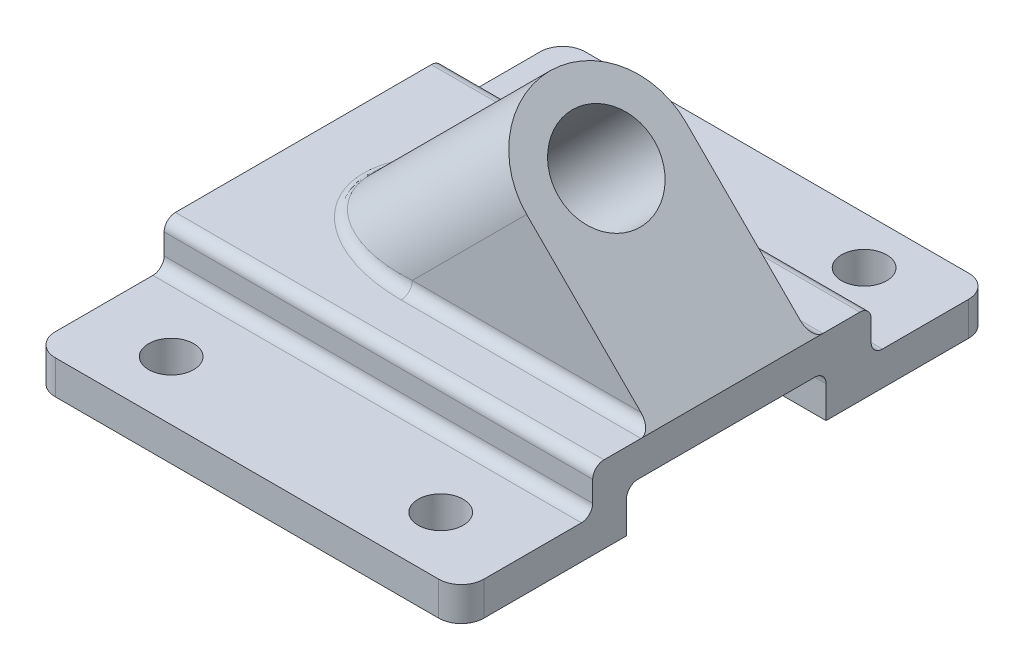
SolidWorks part; units mm, degrees
ref_plane "Front Plane" through (0, 0, 0) normal (0, 0, 1) x (1, 0, 0)
ref_plane "Top Plane" through (0, 0, 0) normal (0, 1, 0) x (1, 0, 0)
ref_plane "Right Plane" through (0, 0, 0) normal (1, 0, 0) x (0, 0, -1)
sketch "Sketch9" plane through (0, 0, 0) normal (1, 0, 0) x (0, 0, -1)
  line L0 (10.005, 0) -> (56.5219, 0)
  line L1 (56.5219, 0) -> (56.5219, 9.0116)
  line L2 (59.6969, 12.1866) -> (109.5164, 12.1866)
  line L3 (10.005, 9.525) -> (43.8219, 9.525)
  line L4 (46.9969, 12.7) -> (46.9969, 18.5366)
  line L5 (50.1719, 21.7116) -> (122.2164, 21.7116)
  line L6 (46.9969, 21.7116) -> (96.2968, 21.7116) construction
  line L7 (46.9969, 9.525) -> (46.9969, 21.7116) construction
  line L8 (0, 9.525) -> (46.9969, 9.525) construction
  line L9 (125.3914, 12.7) -> (125.3914, 18.5366)
  line L10 (159.2084, 9.525) -> (128.5664, 9.525)
  line L11 (112.6914, 0) -> (112.6914, 9.0116)
  line L12 (159.2084, 0) -> (112.6914, 0)
  line L13 (10.005, 9.525) -> (10.005, 0)
  line L14 (159.2084, 9.525) -> (159.2084, 0)
  line L15 (56.5219, 0) -> (56.5219, 12.1866) construction
  line L17 (0, 0) -> (56.5219, 0) construction
  line L18 (56.5219, 12.1866) -> (96.2968, 12.1866) construction
  arc A0 (50.1719, 21.7116) -> (46.9969, 18.5366) centre (50.1719, 18.5366) ccw
  arc A1 (46.9969, 12.7) -> (43.8219, 9.525) centre (43.8219, 12.7) cw
  arc A2 (125.3914, 12.7) -> (128.5664, 9.525) centre (128.5664, 12.7) ccw
  arc A3 (122.2164, 21.7116) -> (125.3914, 18.5366) centre (122.2164, 18.5366) cw
  arc A4 (59.6969, 12.1866) -> (56.5219, 9.0116) centre (59.6969, 9.0116) ccw
  arc A5 (109.5164, 12.1866) -> (112.6914, 9.0116) centre (109.5164, 9.0116) cw
  point P21 (86.1942, 21.7116)
  point P25 (84.6067, 12.1866)
  dimension "D2" = 3.175
  dimension "D3" = 3.175
  dimension "D1" = 9.525
extrude "Extrude5" add sketch "Sketch9" against normal blind 120.65
fillet "Fillet1" radius 6.35 4 edges at (-120.65, 4.7625, -159.2084) (0, 4.7625, -159.2084) (-120.65, 4.7625, -10.005) (0, 4.7625, -10.005)
ref_plane "Plane3" through (10.8558, 10.8558, 0) normal (0.7071, 0.7071, 0) x (0, 0, -1)
sketch "Sketch10" plane through (10.8558, 10.8558, 0) normal (0.7071, 0.7071, 0) x (0, 0, -1)
  line L1 (122.2164, 15.3524) -> (50.1719, 15.3524) construction
  line L2 (108.6293, 65.3527) -> (108.6293, 15.3524)
  line L3 (63.7591, 65.3527) -> (63.7591, 15.3524)
  line L4 (63.7591, 15.3524) -> (108.6293, 15.3524)
  arc A0 (108.6293, 65.3527) -> (63.7591, 65.3527) centre (86.1942, 65.3527) ccw
  circle A1 centre (86.1942, 65.3527) radius 13.5097
extrude "Extrude6" add sketch "Sketch10" against normal up to body
sketch "Sketch11" plane through (10.8558, 10.8558, 0) normal (0.7071, 0.7071, 0) x (0, 0, -1)
  circle A0 centre (86.1942, 65.3527) radius 13.5097 construction
  circle A1 centre (86.1942, 65.3527) radius 13.5097
extrude "Extrude7" cut sketch "Sketch11" against normal blind 114.3
fillet "Fillet2" radius 3.175 3 edges at (-35.3555, 21.7116, -108.6293) (-102.439, 21.7116, -86.1942) (-35.3555, 21.7116, -63.7591)
ref_plane "Plane4" through (0, 9.525, 0) normal (0, 1, 0) x (-1, 0, 0)
sketch "Sketch12" plane through (0, 9.525, 0) normal (0, 1, 0) x (-1, 0, 0)
  line L0 (0, -26.5905) -> (22.3895, -26.5905) construction
  line L1 (0, -43.8219) -> (0, -16.355) construction
  line L2 (60.325, -10.005) -> (60.325, -43.8219) construction
  line L3 (114.3, -10.005) -> (6.35, -10.005) construction
  line L4 (120.65, -43.8219) -> (0, -43.8219) construction
  line L5 (0, -86.1942) -> (143.7584, -86.1942) construction
  line L6 (0, -60.5841) -> (0, -111.8043) construction
  circle A0 centre (22.3895, -26.5905) radius 6.35
  circle A1 centre (98.2605, -26.5905) radius 6.35
  circle A2 centre (98.2605, -145.7978) radius 6.35
  circle A3 centre (22.3895, -145.7978) radius 6.35
extrude "Extrude8" cut sketch "Sketch12" against normal blind 114.3
